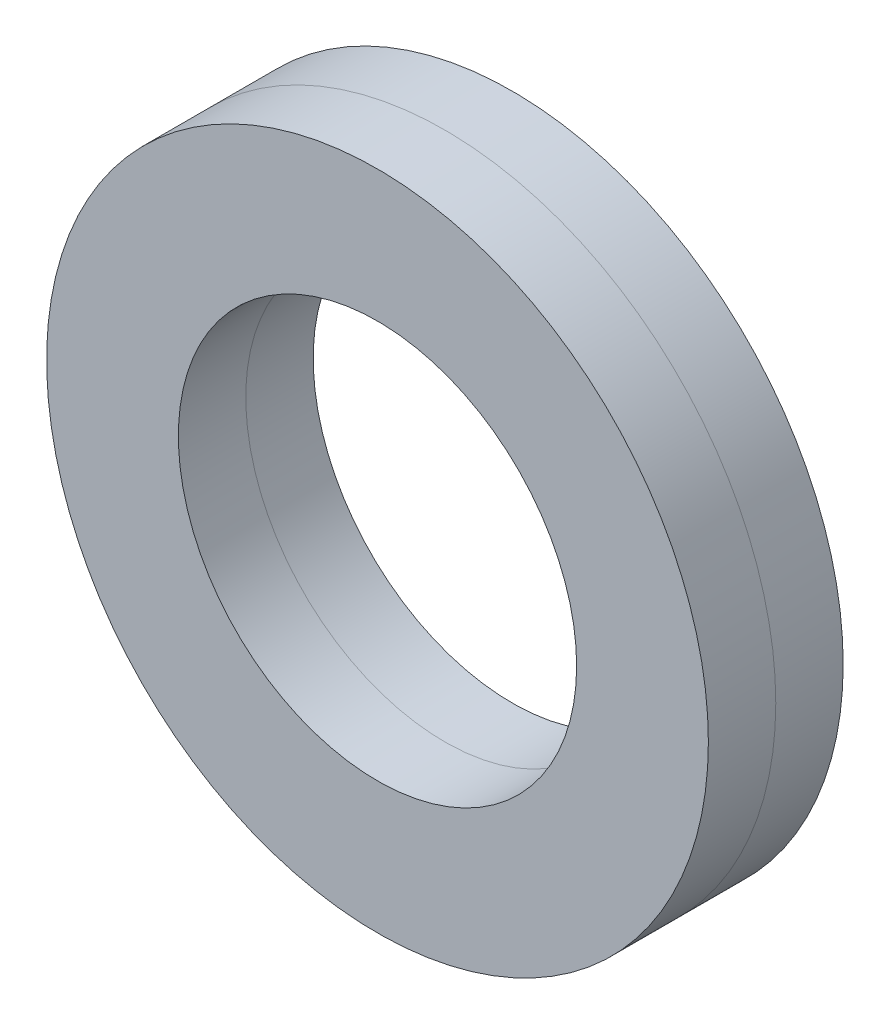
SolidWorks part; units mm, degrees
ref_plane "前视基准面" through (0, 0, 0) normal (0, 0, 1) x (1, 0, 0)
ref_plane "上视基准面" through (0, 0, 0) normal (0, 1, 0) x (1, 0, 0)
ref_plane "右视基准面" through (0, 0, 0) normal (1, 0, 0) x (0, 0, -1)
sketch "草图8" plane through (0, 0, 0) normal (1, 0, 0) x (0, 0, -1)
  line L0 (0, -5.4) -> (0, 5.4)
  line L1 (-1.1, 5.4) -> (1.1, 5.4)
  line L2 (1.1, 5.4) -> (1.1, 3.25)
  line L3 (1.1, 3.25) -> (-1.1, 3.25)
  line L4 (0, 0) -> (1.1754, 0)
  line L5 (-1.1, 5.4) -> (-1.1, 3.25)
  line L6 (-1.1, -5.4) -> (1.1, -5.4)
  line L7 (1.1, -3.25) -> (-1.1, -3.25)
  line L8 (-1.1, 3.25) -> (-1.1, -5.4)
  line L9 (1.1, 3.25) -> (1.1, -5.4)
  point P9 (0, 3.25)
  dimension "D1" = 6.5
  dimension "D2" = 10.8
  dimension "D3" = 2.2
revolve "旋转3" add sketch "草图8" angle 360 about L4 region at (0, 4.325, 0.55)
revolve "旋转4" add sketch "草图8<8>" angle 360 about L4 region at (0, 4.325, -0.55)
sketch "草图8<8>" plane through (0, 0, 0) normal (1, 0, 0) x (0, 0, -1) same geometry as "草图8"
